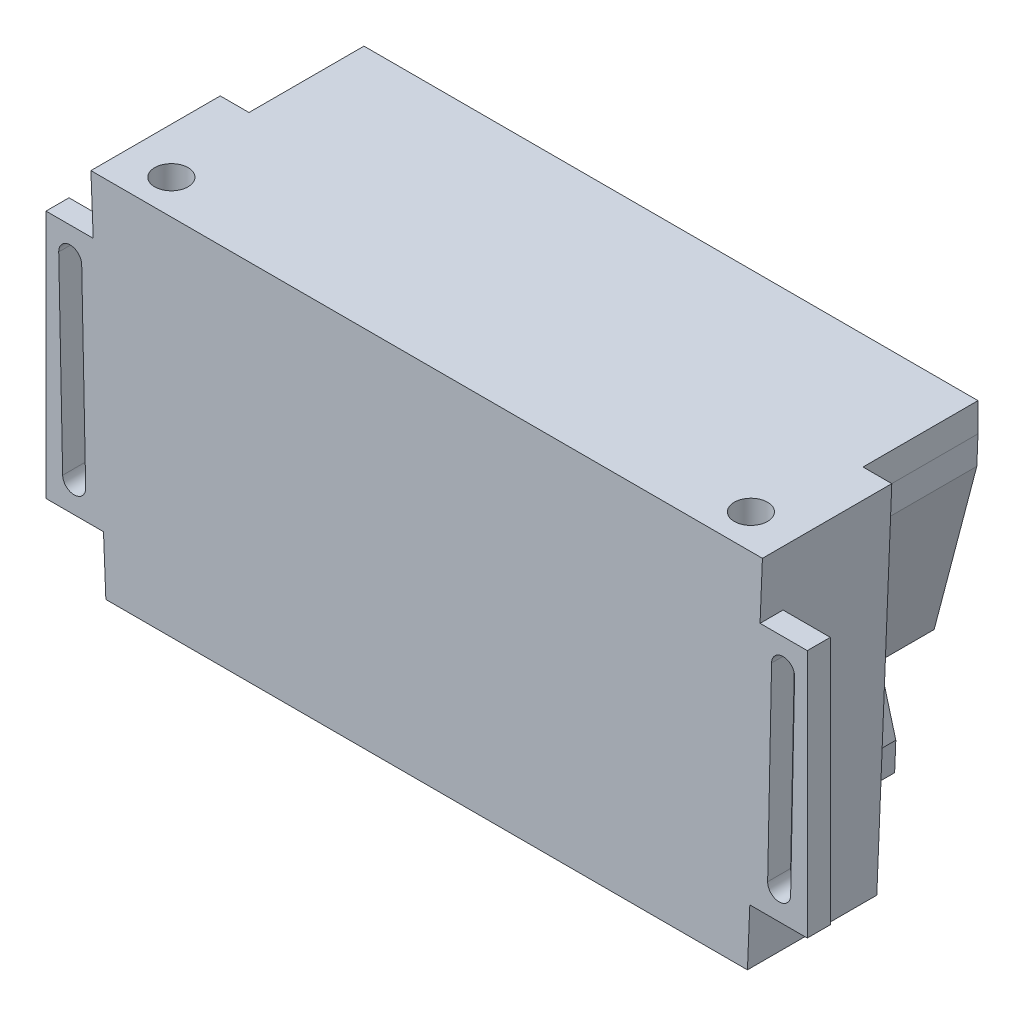
SolidWorks part; units mm, degrees
ref_plane "Front Plane" through (0, 0, 0) normal (0, 0, 1) x (1, 0, 0)
ref_plane "Top Plane" through (0, 0, 0) normal (0, 1, 0) x (1, 0, 0)
ref_plane "Right Plane" through (0, 0, 0) normal (1, 0, 0) x (0, 0, -1)
sketch "Sketch1" plane through (0, 0, 0) normal (0, 0, 1) x (1, 0, 0)
  line L0 (0, 0) -> (5.2, 0)
  line L1 (5.2, 0) -> (7.6, 58.3)
  line L2 (7.6, 58.3) -> (-2.4, 58.3)
  line L3 (-2.4, 58.3) -> (0, 0)
  line L4 (2.6, 58.3) -> (2.6, 0) construction
  line L5 (-1.0292, 25) -> (6.2292, 25)
  line L10 (9.7, 58.3) -> (12.1, 0)
  line L15 (12.1, 0) -> (17.3, 0)
  line L20 (17.3, 0) -> (19.7, 58.3)
  line L25 (19.7, 58.3) -> (9.7, 58.3)
  line L30 (12.0708, 25) -> (19.4942, 53.3)
  line L35 (12.0708, 25) -> (17.5058, 5)
  line L40 (11.0708, 25) -> (18.3292, 25)
  line L45 (21.8, 58.3) -> (24.2, 0)
  line L46 (-0.0292, 25) -> (5.4058, 5)
  line L47 (-0.0292, 25) -> (7.3942, 53.3)
  line L48 (24.2, 0) -> (29.4, 0)
  line L49 (29.4, 0) -> (31.8, 58.3)
  line L50 (31.8, 58.3) -> (21.8, 58.3)
  line L51 (24.1708, 25) -> (31.5942, 53.3)
  line L52 (24.1708, 25) -> (29.6058, 5)
  line L53 (23.1708, 25) -> (30.4292, 25)
  line L54 (33.9, 58.3) -> (36.3, 0)
  line L55 (36.3, 0) -> (41.5, 0)
  line L56 (41.5, 0) -> (43.9, 58.3)
  line L57 (43.9, 58.3) -> (33.9, 58.3)
  line L58 (36.2708, 25) -> (43.6942, 53.3)
  line L59 (36.2708, 25) -> (41.7058, 5)
  line L60 (35.2708, 25) -> (42.5292, 25)
  line L61 (46, 58.3) -> (48.4, 0)
  line L62 (48.4, 0) -> (53.6, 0)
  line L63 (53.6, 0) -> (56, 58.3)
  line L64 (56, 58.3) -> (46, 58.3)
  line L65 (48.3708, 25) -> (55.7942, 53.3)
  line L66 (48.3708, 25) -> (53.8058, 5)
  line L67 (47.3708, 25) -> (54.6292, 25)
  line L68 (58.1, 58.3) -> (60.5, 0)
  line L69 (60.5, 0) -> (65.7, 0)
  line L70 (65.7, 0) -> (68.1, 58.3)
  line L71 (68.1, 58.3) -> (58.1, 58.3)
  line L72 (60.4708, 25) -> (67.8942, 53.3)
  line L73 (60.4708, 25) -> (65.9058, 5)
  line L74 (59.4708, 25) -> (66.7292, 25)
  line L75 (70.2, 58.3) -> (72.6, 0)
  line L76 (72.6, 0) -> (77.8, 0)
  line L77 (77.8, 0) -> (80.2, 58.3)
  line L78 (80.2, 58.3) -> (70.2, 58.3)
  line L79 (72.5708, 25) -> (79.9942, 53.3)
  line L80 (72.5708, 25) -> (78.0058, 5)
  line L81 (71.5708, 25) -> (78.8292, 25)
  line L82 (82.3, 58.3) -> (84.7, 0)
  line L83 (84.7, 0) -> (89.9, 0)
  line L84 (89.9, 0) -> (92.3, 58.3)
  line L85 (92.3, 58.3) -> (82.3, 58.3)
  line L86 (84.6708, 25) -> (92.0942, 53.3)
  line L87 (84.6708, 25) -> (90.1058, 5)
  line L88 (83.6708, 25) -> (90.9292, 25)
  line L89 (94.4, 58.3) -> (96.8, 0)
  line L90 (96.8, 0) -> (102, 0)
  line L91 (102, 0) -> (104.4, 58.3)
  line L92 (104.4, 58.3) -> (94.4, 58.3)
  line L93 (96.7708, 25) -> (104.1942, 53.3)
  line L94 (96.7708, 25) -> (102.2058, 5)
  line L95 (95.7708, 25) -> (103.0292, 25)
  dimension "D1" = 5.2
  dimension "D2" = 10
  dimension "D3" = 58.3
  dimension "D4" = 25
  dimension "D6" = 2.1
  dimension "D7" = 5
  dimension "D8" = 5
  dimension "D9" = 1
  dimension "D5" = 9
extrude "Boss-Extrude1" add sketch "Sketch1" along normal blind 20 contours L4 L2 L3 L5 L47 | L2 L4 L47 L1 | L10 L40 L30 L20 L25 | L45 L53 L51 L49 L50 | L54 L60 L58 L56 L57 | L61 L67 L65 L63 L64 | L68 L74 L72 L70 L71 | L75 L81 L79 L77 L78 | L82 L88 L86 L84 L85 | L89 L95 L93 L91 L92 | L88 L82 L83 L84 L87 | L81 L75 L76 L77 L80 | L74 L68 L69 L70 L73 | L67 L61 L62 L63 L66 | L60 L54 L55 L56 L59 | L53 L45 L48 L49 L52 | L40 L10 L15 L20 L35
sketch "Sketch2" plane through (0, 58.3, 0) normal (0, 1, 0) x (1, 0, 0)
  line L0 (104.4, -20) -> (94.4, -20) construction
  line L1 (104.4, 0) -> (-2.4, 0)
  line L2 (104.4, 0) -> (104.4, -20)
  line L3 (104.4, -20) -> (-2.4, -20)
  line L4 (-2.4, 0) -> (-2.4, -20)
extrude "Boss-Extrude2" add sketch "Sketch2" along normal blind 5
sketch "Sketch3" plane through (0, 0, 20) normal (0, 0, 1) x (1, 0, 0)
  line L0 (109.4042, 63.3) -> (107.0042, 5)
  line L1 (107.0042, 5) -> (-5, 5)
  line L2 (-5, 5) -> (-7.4, 63.3)
  line L3 (-7.4, 63.3) -> (109.4042, 63.3)
  line L6 (-2.4, 63.3) -> (104.4, 63.3) construction
  line L7 (-2.4, 58.3) -> (-1.0292, 25) construction
  line L9 (104.1942, 53.3) -> (104.4, 58.3) construction
  dimension "D1" = 5
  dimension "D2" = 5
  dimension "D3" = 5.0042
extrude "Boss-Extrude3" add sketch "Sketch3" along normal blind 12.5
sketch "Sketch4" plane through (0, 0, 32.5) normal (0, 0, 1) x (1, 0, 0)
  line L0 (107.0042, 5) -> (-5, 5)
  line L1 (-5, 5) -> (-5.2058, 10)
  line L2 (-7.4, 63.3) -> (-5, 5) construction
  line L3 (-5.2058, 10) -> (107.2101, 10)
  line L4 (107.0042, 5) -> (109.4042, 63.3) construction
  line L5 (107.2101, 10) -> (107.0042, 5)
  line L6 (107.2101, 10) -> (109.4042, 63.3)
  line L7 (109.4042, 63.3) -> (106.4042, 63.3)
  line L8 (109.4042, 63.3) -> (-7.4, 63.3) construction
  line L9 (106.4042, 63.3) -> (106.4042, 10)
  line L10 (106.4042, 10) -> (107.2101, 10)
  line L11 (-5.2058, 10) -> (-7.4, 63.3)
  line L12 (-7.4, 63.3) -> (-4.4, 63.3)
  line L13 (-4.4, 63.3) -> (-4.4, 10)
  line L14 (-4.4, 10) -> (-5.2058, 10)
  line L15 (-7.4, 63.3) -> (-5, 5) construction
  line L16 (5.6, 10) -> (96.4042, 10)
  line L17 (5.6, 10) -> (5.6, 63.3)
  line L18 (5.6, 63.3) -> (96.4042, 63.3)
  line L19 (96.4042, 10) -> (96.4042, 63.3)
  point P25 (51.0021, 10)
  point P26 (51.0021, 63.3)
  line M13 (109.4042, 63.3) -> (-7.4, 63.3)
  line M14 (-7.4, 63.3) -> (-5, 5)
  line M15 (-5, 5) -> (107.0042, 5)
  line M16 (107.0042, 5) -> (109.4042, 63.3)
  dimension "D1" = 5
  dimension "D2" = 3
  dimension "D3" = 10
extrude "Boss-Extrude4" add sketch "Sketch4" along normal blind 10 contours L3 M14 M15 M16 | L13 L3 M13 M14 | L6 L7 L9 L10 | L17 L16 L19 L18 region at (51.0021, 7.5015, 32.5) region at (-5.4569, 41.7715, 32.5)
sketch "Sketch7" plane through (0, 10, 0) normal (0, 1, 0) x (1, 0, 0)
  line L0 (101.4042, -42.5) -> (101.4042, -32.5) construction
  line L1 (96.4042, -42.5) -> (106.4042, -42.5) construction
  line L2 (96.4042, -32.5) -> (106.4042, -32.5) construction
  line L3 (0.6, -42.5) -> (0.6, -32.5) construction
  line L4 (-4.4, -42.5) -> (5.6, -42.5) construction
  line L5 (-4.4, -32.5) -> (5.6, -32.5) construction
  circle A0 centre (101.4042, -36.5) radius 2.9
  circle A1 centre (0.6, -36.5) radius 2.9
  dimension "D1" = 5.8
  dimension "D2" = 4
extrude "Cut-Extrude3" cut sketch "Sketch7" against normal through all
sketch "Sketch8" plane through (0, 10, 0) normal (0, 1, 0) x (1, 0, 0)
  line L4 (96.4042, -42.5) -> (106.4042, -42.5)
  line L5 (106.4042, -42.5) -> (106.4042, -32.5)
  line L6 (106.4042, -32.5) -> (96.4042, -32.5)
  line L7 (96.4042, -32.5) -> (96.4042, -42.5)
  line L8 (96.4042, -42.5) -> (106.4042, -42.5)
  line L9 (106.4042, -42.5) -> (106.4042, -32.5)
  line L10 (106.4042, -32.5) -> (96.4042, -32.5)
  line L11 (96.4042, -32.5) -> (96.4042, -42.5)
  line L12 (-4.4, -42.5) -> (5.6, -42.5)
  line L13 (5.6, -42.5) -> (5.6, -32.5)
  line L14 (5.6, -32.5) -> (-4.4, -32.5)
  line L15 (-4.4, -32.5) -> (-4.4, -42.5)
  line L16 (-4.4, -42.5) -> (5.6, -42.5)
  line L17 (5.6, -42.5) -> (5.6, -32.5)
  line L18 (5.6, -32.5) -> (-4.4, -32.5)
  line L19 (-4.4, -32.5) -> (-4.4, -42.5)
  circle A0 centre (101.4042, -36.5) radius 2.9 construction
  circle A1 centre (101.4042, -36.5) radius 2.9
  circle A2 centre (0.6, -36.5) radius 2.9 construction
  circle A3 centre (0.6, -36.5) radius 2.9
  dimension "D1" = 0
  dimension "D2" = 0
extrude "Boss-Extrude6" add sketch "Sketch8" along normal up to surface (53.3 mm away) up to face at (51.0016, 63.3, 29.0625)
sketch "Sketch10" plane through (0, 0, 20) normal (0, 0, 1) x (1, 0, 0)
  line L1 (107.0042, 5) -> (109.4042, 63.3) construction
  line L2 (84.7, 0) -> (89.9, 0) construction
  line L23 (-4.7942, 0) -> (106.7984, 0)
  line L24 (-4.7942, 0) -> (-5, 5)
  line L25 (-5, 5) -> (107.0042, 5)
  line L26 (106.7984, 0) -> (107.0042, 5)
  line L27 (-5, 5) -> (11.8942, 5) construction
  line L28 (-7.4, 63.3) -> (-5, 5) construction
extrude "Boss-Extrude7" add sketch "Sketch10" along normal up to surface (22.5 mm away) contours L24 | L25 L23 | L24 | L26 | L26 region at (51.0021, 2.5015, 20) up to face at (51.0021, 34.15, 42.5)
sketch "Sketch12" plane through (0, 5, 0) normal (0, 1, 0) x (1, 0, 0)
  circle A1 centre (101.4042, -36.5) radius 2.9
  circle A2 centre (101.4042, -36.5) radius 2.9
  circle A3 centre (0.6, -36.5) radius 2.9
  circle A4 centre (0.6, -36.5) radius 2.9
  dimension "D1" = 0
  dimension "D2" = 0
extrude "Cut-Extrude6" cut sketch "Sketch12" against normal through all
sketch "Sketch13" plane through (0, 0, 42.5) normal (0, 0, 1) x (1, 0, 0)
  line L0 (112.2101, 10) -> (113.1013, 53.3) construction
  line L5 (108.9926, 53.3) -> (107.2101, 10)
  line L6 (106.7984, 0) -> (109.4042, 63.3) construction
  line L9 (107.2101, 10) -> (117.2101, 10)
  line L10 (117.2101, 10) -> (117.2101, 53.3)
  line L13 (117.2101, 53.3) -> (108.9926, 53.3)
  line L14 (112.313, 15) -> (112.9984, 48.3) construction
  line L15 (110.3134, 15.0412) -> (110.9988, 48.3412)
  line L16 (114.3126, 14.9588) -> (114.998, 48.2588)
  line L17 (51.0021, 63.3) -> (51.0021, 0) construction
  line L18 (109.4042, 63.3) -> (-7.4, 63.3) construction
  line L19 (-4.7942, 0) -> (106.7984, 0) construction
  line L20 (-10.3087, 15) -> (-10.9942, 48.3) construction
  line L21 (-8.3092, 15.0412) -> (-8.9946, 48.3412)
  line L22 (-12.3083, 14.9588) -> (-12.9937, 48.2588)
  line L23 (-15.2058, 10) -> (-15.2058, 53.3)
  line L24 (-5.2058, 10) -> (-15.2058, 10)
  line L25 (-6.9883, 53.3) -> (-5.2058, 10)
  line L26 (-15.2058, 53.3) -> (-6.9883, 53.3)
  arc A0 (110.3134, 15.0412) -> (114.3126, 14.9588) centre (112.313, 15) ccw
  arc A1 (114.998, 48.2588) -> (110.9988, 48.3412) centre (112.9984, 48.3) ccw
  arc A2 (-8.3092, 15.0412) -> (-12.3083, 14.9588) centre (-10.3087, 15) cw
  arc A3 (-12.9937, 48.2588) -> (-8.9946, 48.3412) centre (-10.9942, 48.3) cw
  point P12 (112.6557, 31.65)
  point P25 (-10.6515, 31.65)
  dimension "D1" = 10
  dimension "D2" = 10
  dimension "D3" = 10
  dimension "D4" = 5
  dimension "D5" = 5
  dimension "D6" = 4
extrude "Boss-Extrude8" add sketch "Sketch13" against normal blind 4
